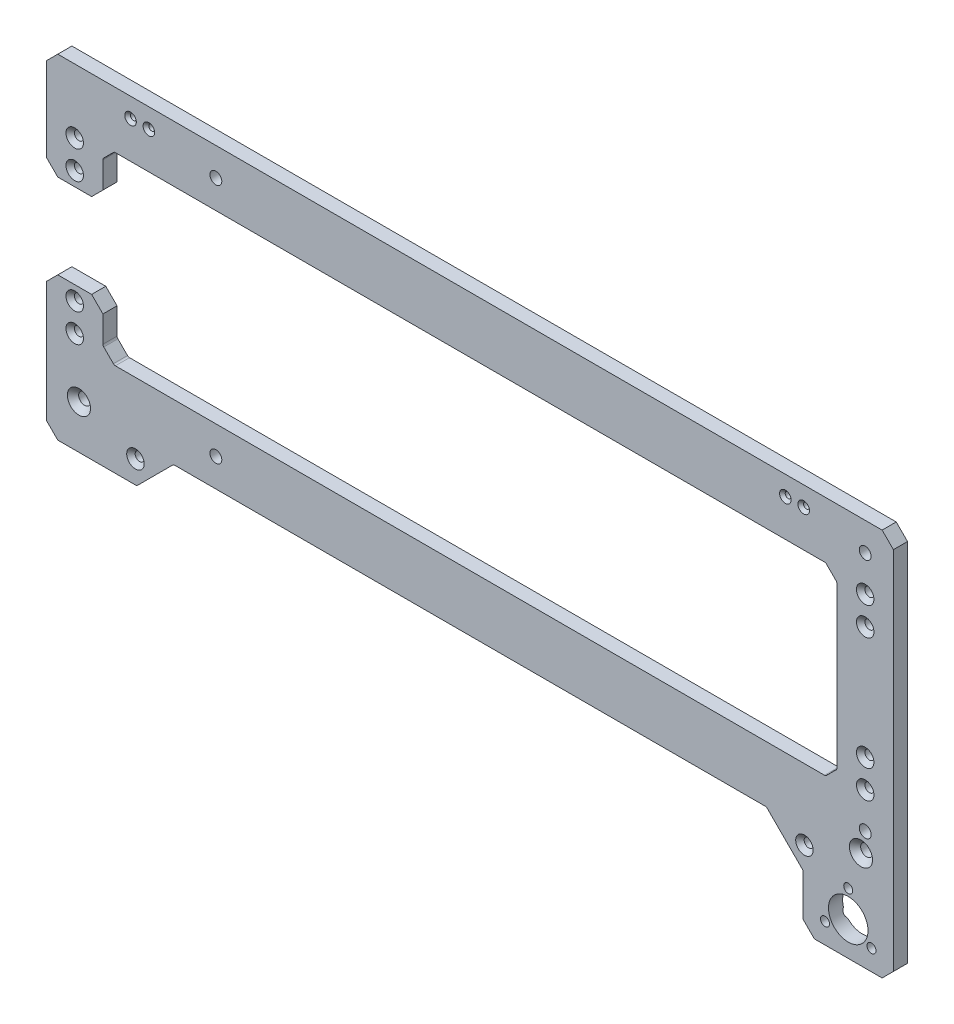
SolidWorks part; units mm, degrees
ref_plane "前视基准面" through (0, 0, 0) normal (0, 0, 1) x (1, 0, 0)
ref_plane "上视基准面" through (0, 0, 0) normal (0, 1, 0) x (1, 0, 0)
ref_plane "右视基准面" through (0, 0, 0) normal (1, 0, 0) x (0, 0, -1)
sketch "草图1" plane through (0, 0, 0) normal (0, 0, 1) x (1, 0, 0)
  line L1 (150, -52.7) -> (-150, -52.7)
  line L2 (150, -52.7) -> (150, 52.7)
  line L3 (150, 52.7) -> (-150, 52.7)
  line L4 (-150, -52.7) -> (-150, 52.7)
  line L5 (150, -52.7) -> (-150, 52.7) construction
  line L6 (150, 52.7) -> (-150, -52.7) construction
  line L7 (130, -32.7) -> (-130, -32.7)
  line L8 (130, -32.7) -> (130, 32.7)
  line L9 (130, 32.7) -> (-130, 32.7)
  line L10 (-130, -32.7) -> (-130, 32.7)
  line L11 (130, -32.7) -> (-130, 32.7) construction
  line L12 (130, 32.7) -> (-130, -32.7) construction
  point P0 (0, 0)
  point P5 (0, 0)
  dimension "D1" = 300
  dimension "D2" = 105.4
  dimension "D3" = 20
  dimension "D4" = 20
extrude "凸台-拉伸1" add sketch "草图1" along normal mid plane 5
sketch "草图2" plane through (0, 0, 2.5) normal (0, 0, 1) x (1, 0, 0)
  line L0 (150, -52.7) -> (150, 52.7) construction
  line L1 (140, -42.7) -> (-90, -42.7) construction
  line L2 (140, -42.7) -> (140, 42.7) construction
  line L3 (140, 42.7) -> (-90, 42.7) construction
  line L4 (-90, -42.7) -> (-90, 42.7) construction
  line L5 (140, -42.7) -> (-90, 42.7) construction
  line L6 (140, 42.7) -> (-90, -42.7) construction
  line L7 (150, 52.7) -> (-150, 52.7) construction
  circle A0 centre (-90, 42.7) radius 2.1
  circle A1 centre (140, 42.7) radius 2.1
  circle A2 centre (-90, -42.7) radius 2.1
  circle A3 centre (140, -42.7) radius 2.1
  point P0 (25, 0)
  dimension "D1" = 10
  dimension "D4" = 4.2
  dimension "D2" = 10
  dimension "D3" = 240
extrude "切除-拉伸1" cut sketch "草图2" against normal through all
sketch "草图3" plane through (0, 0, 2.5) normal (0, 0, 1) x (1, 0, 0)
  line L0 (140, -30) -> (140, 30) construction
  line L1 (150, -52.7) -> (150, 52.7) construction
  line L3 (0, 52.7) -> (0, -52.7) construction
  line L4 (150, 52.7) -> (-150, 52.7) construction
  line L5 (-150, -52.7) -> (150, -52.7) construction
  circle A0 centre (140, 30) radius 1.6
  circle A1 centre (140, -30) radius 1.6
  circle A2 centre (140, 20) radius 1.6
  circle A3 centre (140, -20) radius 1.6
  circle A5 centre (-140, -30) radius 1.6
  circle A6 centre (-140, -20) radius 1.6
  circle A7 centre (-140, 20) radius 1.6
  circle A8 centre (-140, 30) radius 1.6
  point P3 (140, 0)
  dimension "D4" = 3.2
  dimension "D1" = 10
  dimension "D2" = 10
  dimension "D3" = 10
  dimension "D5" = 40
extrude "切除-拉伸2" cut sketch "草图3" against normal through all
chamfer "倒角1" distance 1.5 angle 45 8 edges at (141.6, 30, 2.5) (141.6, 20, 2.5) (141.6, -20, 2.5) (141.6, -30, 2.5) (-141.6, -30, 2.5) (-141.6, -20, 2.5) (-141.6, 20, 2.5) (-141.6, 30, 2.5)
chamfer "倒角2" distance 2 angle 45 4 edges at (-87.9, 42.7, -2.5) (142.1, 42.7, -2.5) (142.1, -42.7, -2.5) (-87.9, -42.7, -2.5)
sketch "草图5" plane through (0, 0, -2.5) normal (0, 0, -1) x (-1, 0, 0)
  line L1 (130, 15) -> (150, 15)
  line L2 (130, 15) -> (130, -15)
  line L3 (130, -15) -> (150, -15)
  line L4 (150, 15) -> (150, -15)
  line L6 (150, 52.7) -> (150, -52.7) construction
  line L7 (130, 32.7) -> (130, -32.7) construction
  circle A0 centre (-140, 20) radius 1.6 construction
  point P10 (150, 0)
  dimension "D1" = 5
extrude "切除-拉伸5" cut sketch "草图5" against normal through all contours L1 L4 L3 L2
sketch "草图6" plane through (0, 0, -2.5) normal (0, 0, -1) x (-1, 0, 0)
  line L0 (150, -52.7) -> (150, -65.7)
  line L1 (150, -65.7) -> (118, -65.7)
  line L2 (118, -65.7) -> (105, -52.7)
  line L3 (150, -52.7) -> (-150, -52.7) construction
  line L4 (105, -52.7) -> (150, -52.7)
  line L5 (0, 0) -> (0, -52.7) construction
  line L6 (-118, -65.7) -> (-105, -52.7)
  line L7 (-150, -65.7) -> (-118, -65.7)
  line L8 (-150, -52.7) -> (-150, -65.7)
  line L9 (-105, -52.7) -> (-150, -52.7)
  dimension "D1" = 13
  dimension "D2" = 32
  dimension "D3" = 45
extrude "凸台-拉伸2" add sketch "草图6" against normal up to surface (5 mm away) up to face at (143.1, 30, 2.5)
sketch "草图7" plane through (0, 0, -2.5) normal (0, 0, -1) x (-1, 0, 0)
  line L0 (118.4853, -57.7) -> (-118.4853, -57.7) construction
  line L1 (-150, -65.7) -> (-118, -65.7) construction
  line L2 (-118, -65.7) -> (-105, -52.7) construction
  line L3 (118, -65.7) -> (150, -65.7) construction
  line L5 (0, -57.7) -> (0, 0) construction
  line L6 (150, -15) -> (150, -65.7) construction
  circle A0 centre (118.4853, -57.7) radius 1.6
  circle A1 centre (-118.4853, -57.7) radius 1.6
  circle A2 centre (138.5, -50.2) radius 2.1
  circle A3 centre (-138.5, -50.2) radius 2.1
  point P8 (0, -57.7)
  dimension "D1" = 8
  dimension "D2" = 3.2
  dimension "D3" = 6
  dimension "D4" = 4.2
  dimension "D5" = 15.5
  dimension "D6" = 11.5
extrude "切除-拉伸6" cut sketch "草图7" against normal through all
chamfer "倒角4" distance 2 angle 45 2 edges at (-140.6, -50.2, 2.5) (140.6, -50.2, 2.5)
chamfer "倒角5" distance 1.5 angle 45 2 edges at (116.8853, -57.7, 2.5) (-120.0853, -57.7, 2.5)
sketch "草图8" plane through (0, 0, 2.5) normal (0, 0, 1) x (1, 0, 0)
  line L0 (-105, -52.7) -> (105, -52.7) construction
  line L1 (150, -65.7) -> (150, 52.7) construction
  line L2 (150, -65.7) -> (150, -84.7)
  line L3 (150, -84.7) -> (118, -84.7)
  line L4 (118, -84.7) -> (118, -65.7)
  line L5 (118, -65.7) -> (150, -65.7)
  circle A0 centre (138.5, -50.2) radius 11 construction
  circle A1 centre (134, -72.7) radius 9 construction
  circle A2 centre (134, -72.7) radius 9.5 construction
  dimension "D1" = 18
  dimension "D2" = 22
  dimension "D3" = 19
  dimension "D5" = 16
  dimension "D4" = 20
  dimension "D6" = 12
extrude "凸台-拉伸3" add sketch "草图8" against normal up to surface (5 mm away) up to face at (140.6, -50.2, -2.5)
chamfer "倒角3" distance 4 angle 45 13 edges at (-150, 52.7, 0) (-130, -32.7, 0) (-130, 32.7, 0) (150, 52.7, 0) (130, 32.7, 0) (130, -32.7, 0) (-150, 15, 0) (-130, 15, 0) (-150, -15, 0) (-130, -15, 0) (-150, -65.7, 0) (150, -84.7, 0) (118, -84.7, 0)
fillet "圆角1" radius 1 11 edges at (126, -32.7, 0) (130, -28.7, 0) (-126, -32.7, 0) (-130, -28.7, 0) (-130, 28.7, 0) (-126, 32.7, 0) (126, 32.7, 0) (130, 28.7, 0) (-105, -52.7, 0) (105, -52.7, 0) (118, -65.7, 0)
sketch "草图9" plane through (0, 0, 2.5) normal (0, 0, 1) x (1, 0, 0)
  line L0 (122, -84.7) -> (146, -84.7) construction
  line L1 (150, -80.7) -> (150, 48.7) construction
  circle A0 centre (134, -72.7) radius 7
  circle A1 centre (134, -72.7) radius 9.5 construction
  circle A2 centre (134, -63.2) radius 1.6
  circle A3 centre (142.2272, -77.45) radius 1.6
  circle A4 centre (125.7728, -77.45) radius 1.6
  point P16 (134, -72.7)
  dimension "D1" = 12
  dimension "D2" = 16
  dimension "D3" = 14
  dimension "D4" = 19
  dimension "D5" = 3.2
extrude "切除-拉伸7" cut sketch "草图9" against normal through all
chamfer "倒角6" distance 1.5 angle 45 3 edges at (143.8272, -77.45, -2.5) (127.3728, -77.45, -2.5) (135.6, -63.2, -2.5)
sketch "草图10" plane through (0, 0, -2.5) normal (0, 0, -1) x (-1, 0, 0)
  line L0 (130, 28.2858) -> (130, 19) construction
  line L1 (-125.5858, 32.7) -> (125.5858, 32.7) construction
  line L2 (121.5, 33.5) -> (122.4809, 35.7995) construction
  line L3 (122.4809, 35.7995) -> (110.5232, 40.9) construction
  line L4 (110.5232, 40.9) -> (123.4232, 40.9) construction
  line L5 (120.2232, 45.8) -> (113.7232, 45.8) construction
  line L6 (1, 0) -> (1, -32.7) construction
  line L8 (0, 0) -> (0, -32.7) construction
  line L9 (125.5858, -32.7) -> (-125.5858, -32.7) construction
  circle A0 centre (121.5, 33.5) radius 1.5 construction
  circle A1 centre (112.5622, 40.9) radius 0.8 construction
  circle A2 centre (120.2232, 45.8) radius 1.05
  circle A3 centre (113.7232, 45.8) radius 1.05
  circle A4 centre (-111.7232, 45.8) radius 1.05
  circle A5 centre (-118.2232, 45.8) radius 1.05
  point P0 (121.5, 32)
  point P16 (116.9732, 45.8)
  point P17 (116.9732, 40.9)
  dimension "D3" = 3
  dimension "D4" = 12.9
  dimension "D7" = 1.6
  dimension "D8" = 13.8
  dimension "D9" = 6.5
  dimension "D10" = 2.1
  dimension "D1" = 8.5
  dimension "D2" = 0.7
  dimension "D5" = 13
  dimension "D6" = 2.5
  dimension "D11" = 4.9
  dimension "D12" = 1
extrude "切除-拉伸8" cut sketch "草图10" against normal through all
chamfer "倒角7" distance 1 angle 45 4 edges at (112.7732, 45.8, 2.5) (119.2732, 45.8, 2.5) (-121.2732, 45.8, 2.5) (-114.7732, 45.8, 2.5)
equation "\"D3@草图3\"=\"D2@草图3\""
